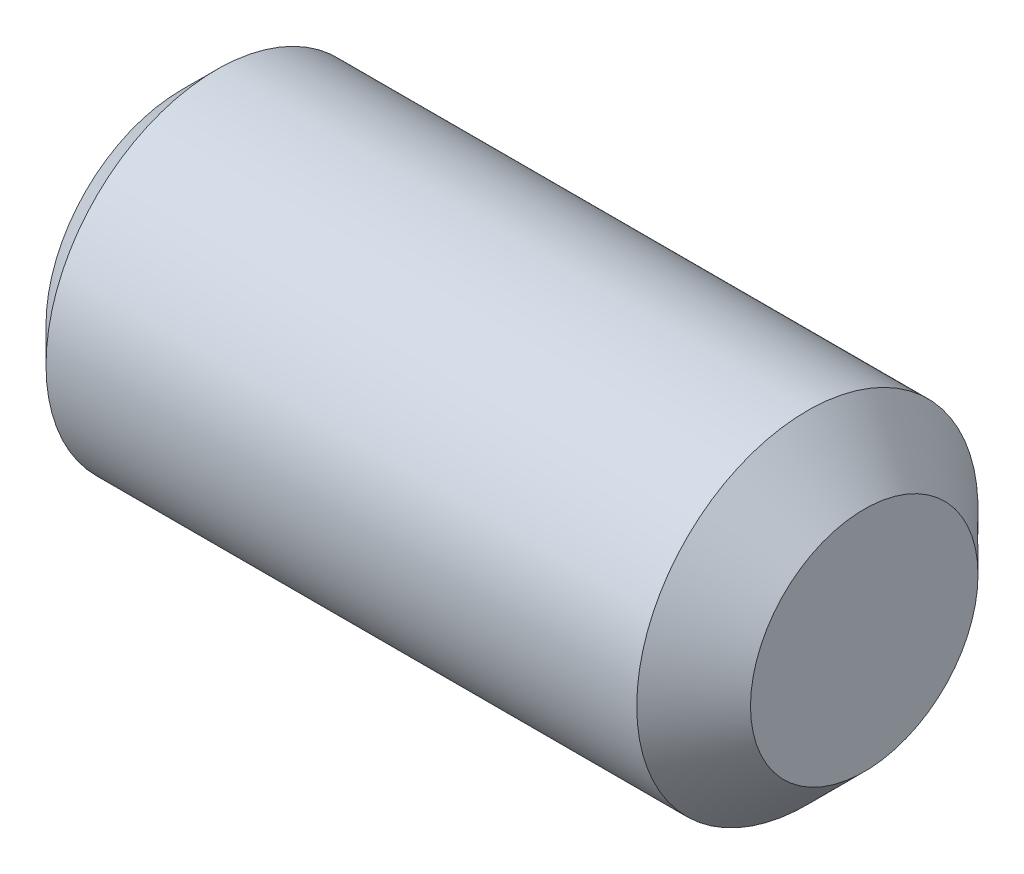
SolidWorks part; units mm, degrees
ref_plane "Front Plane" through (0, 0, 0) normal (0, 0, 1) x (1, 0, 0)
ref_plane "Top Plane" through (0, 0, 0) normal (0, 1, 0) x (1, 0, 0)
ref_plane "Right Plane" through (0, 0, 0) normal (1, 0, 0) x (0, 0, -1)
sketch "Sketch1" plane through (0, 0, 0) normal (1, 0, 0) x (0, 0, -1)
  line L0 (-0.75, -0.433) -> (0, -0.866)
  line L1 (0, -0.866) -> (0.75, -0.433)
  line L2 (0.75, -0.433) -> (0.75, 0.433)
  line L3 (0.75, 0.433) -> (0, 0.866)
  line L4 (0, 0.866) -> (-0.75, 0.433)
  line L5 (-0.75, 0.433) -> (-0.75, -0.433)
sketch "Sketch2" plane through (0, 0, 0) normal (0, 0, 1) x (1, 0, 0)
  line L0 (0, 0) -> (0, 1.1935)
  line L1 (0, 1.1935) -> (0.3065, 1.5)
  line L2 (0.3065, 1.5) -> (5.5, 1.5)
  line L3 (5.5, 1.5) -> (6, 1)
  line L4 (6, 1) -> (6, 0)
  line L5 (6, 0) -> (0, 0)
  line L6 (6, 0) -> (0, 0) construction
revolve "Revolve1" add sketch "Sketch2" angle 360 about L6 reverse direction yes
cosmetic thread "Cosmetic Thread1" parameters "D1"=5.8065, "D2"=2.387
sketch "Sketch3" plane through (0, 0, 0) normal (0, 0, 1) x (1, 0, 0)
  line L0 (0, 0) -> (0, 0.75)
  line L1 (0, 0.75) -> (2, 0.75)
  line L2 (2, 0.75) -> (2, 0)
  line L3 (2, 0) -> (0, 0)
  line L4 (2, 0) -> (0, 0) construction
revolve "Cut-Revolve1" cut sketch "Sketch3" angle 360 about L4 reverse direction yes
sketch "Sketch4" plane through (0, 0, 0) normal (0, 0, 1) x (1, 0, 0)
  line L0 (2, 0) -> (2, 0.75)
  line L1 (2, 0.75) -> (2.433, 0)
  line L2 (2.433, 0) -> (2, 0)
  line L3 (2.433, 0) -> (2, 0) construction
revolve "Cut-Revolve2" cut sketch "Sketch4" angle 360 about L3 reverse direction yes
sketch "Sketch5" plane through (0, 0, 0) normal (0, 0, 1) x (1, 0, 0)
  line L0 (-0.3, 0.75) -> (0.067, 0.75)
  line L1 (0.067, 0.75) -> (0, 0.866)
  line L2 (0, 0.866) -> (-0.3, 0.866)
  line L3 (-0.3, 0.866) -> (-0.3, 0.75)
  line L4 (0, 0) -> (-0.3, 0) construction
revolve "Cut-Revolve3" cut sketch "Sketch5" angle 360 about L4 reverse direction yes
extrude "Cut-Extrude1" cut sketch "Sketch1" along normal blind 2
ref_plane "Plane1" through (4, 0, 0) normal (1, 0, 0) x (0, 0, -1)
ref_plane "Plane2" through (0, 0, 0) normal (1, 0, 0) x (0, 0, -1)
ref_plane "Plane3" through (6, 0, 0) normal (1, 0, 0) x (0, 0, -1)
ref_plane "IP1 XY" through (0, 0, 0) normal (1, 0, 0) x (0, 0, -1)
ref_plane "IP1 XZ" through (0, 0, 0) normal (0, -1, 0) x (-1, 0, 0)
ref_plane "IP1 YZ" through (0, 0, 0) normal (0, 0, -1) x (-1, 0, 0)
ref_axis "IP1 X" through (0, 0, 80.9) along (0, 0, -1)
ref_axis "IP1 Y" through (0, -50, 0) along (0, 1, 0)
ref_axis "IP1 Z" through (80.9, 0, 0) along (-1, 0, 0)
sketch3d "IP1"
  point P0 (0, 0, 0)
ref_plane "IP2 XY" through (6, 0, 0) normal (1, 0, 0) x (0, 0, -1)
ref_plane "IP2 XZ" through (0, 0, 0) normal (0, -1, 0) x (-1, 0, 0)
ref_plane "IP2 YZ" through (0, 0, 0) normal (0, 0, -1) x (-1, 0, 0)
ref_axis "IP2 X" through (6, 0, 80.9) along (0, 0, -1)
ref_axis "IP2 Y" through (6, -50, 0) along (0, 1, 0)
ref_axis "IP2 Z" through (80.9, 0, 0) along (-1, 0, 0)
sketch3d "IP2"
  point P0 (6, 0, 0)
other "Freeze***"
